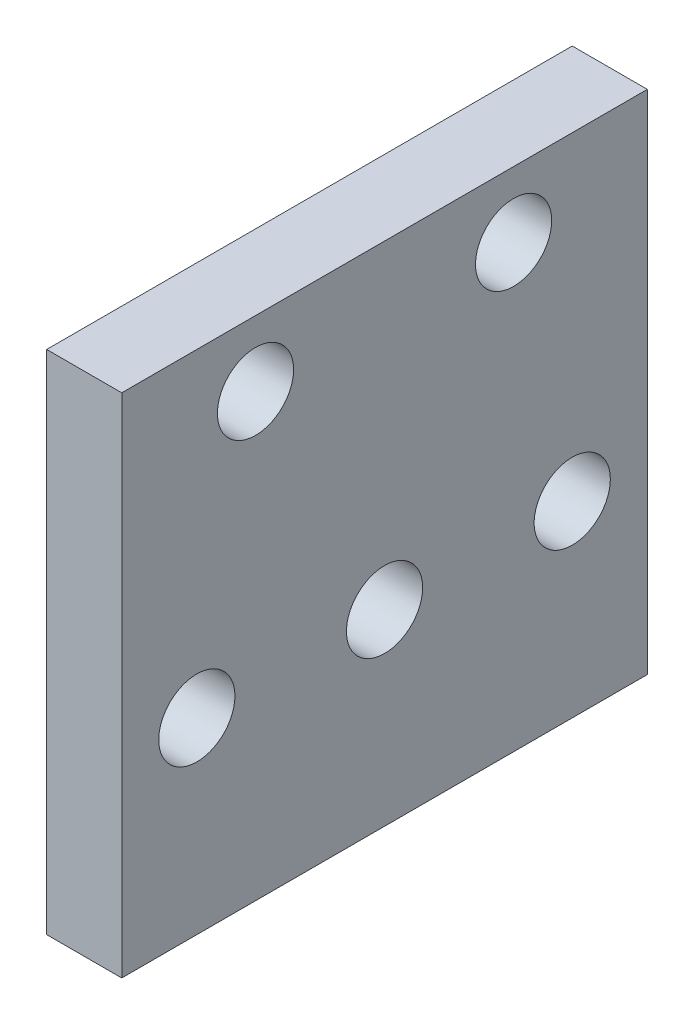
SolidWorks part; units mm, degrees
ref_plane "Front" through (0, 0, 0) normal (0, 0, 1) x (1, 0, 0)
ref_plane "Top" through (0, 0, 0) normal (0, 1, 0) x (1, 0, 0)
ref_plane "Right" through (0, 0, 0) normal (1, 0, 0) x (0, 0, -1)
sketch "Sketch1" plane through (0, 0, 0) normal (1, 0, 0) x (0, 0, -1)
  line L1 (-17.78, -17.145) -> (17.78, -17.145)
  line L2 (-17.78, -17.145) -> (-17.78, 17.145)
  line L3 (-17.78, 17.145) -> (17.78, 17.145)
  line L4 (17.78, -17.145) -> (17.78, 17.145)
  line L5 (-17.78, -17.145) -> (17.78, 17.145) construction
  line L6 (-17.78, 17.145) -> (17.78, -17.145) construction
  point P0 (0, 0)
  dimension "D1" = 35.56
  dimension "D2" = 34.29
extrude "Boss-Extrude1" add sketch "Sketch1" along normal blind 5.08
sketch "Sketch2" plane through (5.08, 0, 0) normal (1, 0, 0) x (0, 0, -1)
  line L0 (-17.78, 8.255) -> (17.78, 8.255) construction
  line L1 (-17.78, 17.145) -> (-17.78, -17.145) construction
  line L2 (17.78, -17.145) -> (17.78, 17.145) construction
  line L3 (-17.78, -17.145) -> (17.78, -17.145) construction
  line L4 (0, 8.255) -> (0, 17.145) construction
  line L5 (17.78, 17.145) -> (-17.78, 17.145) construction
  line L8 (0, 8.255) -> (0, -17.145) construction
  line L9 (-12.7, -4.445) -> (12.7, -4.445) construction
  circle A0 centre (-8.7312, 12.7) radius 2.5781
  circle A1 centre (8.7312, 12.7) radius 2.5781
  circle A2 centre (-12.7, -4.445) radius 2.5781
  circle A3 centre (0, -4.445) radius 2.5781
  circle A4 centre (12.7, -4.445) radius 2.5781
  point P23 (0, -4.445)
  point P28 (0, 12.7)
  dimension "D2" = 5.1562
  dimension "D3" = 5.1562
  dimension "D5" = 5.1562
  dimension "D1" = 25.4
  dimension "D4" = 25.4
  dimension "D6" = 17.4625
extrude "Cut-Extrude1" cut sketch "Sketch2" against normal through all
